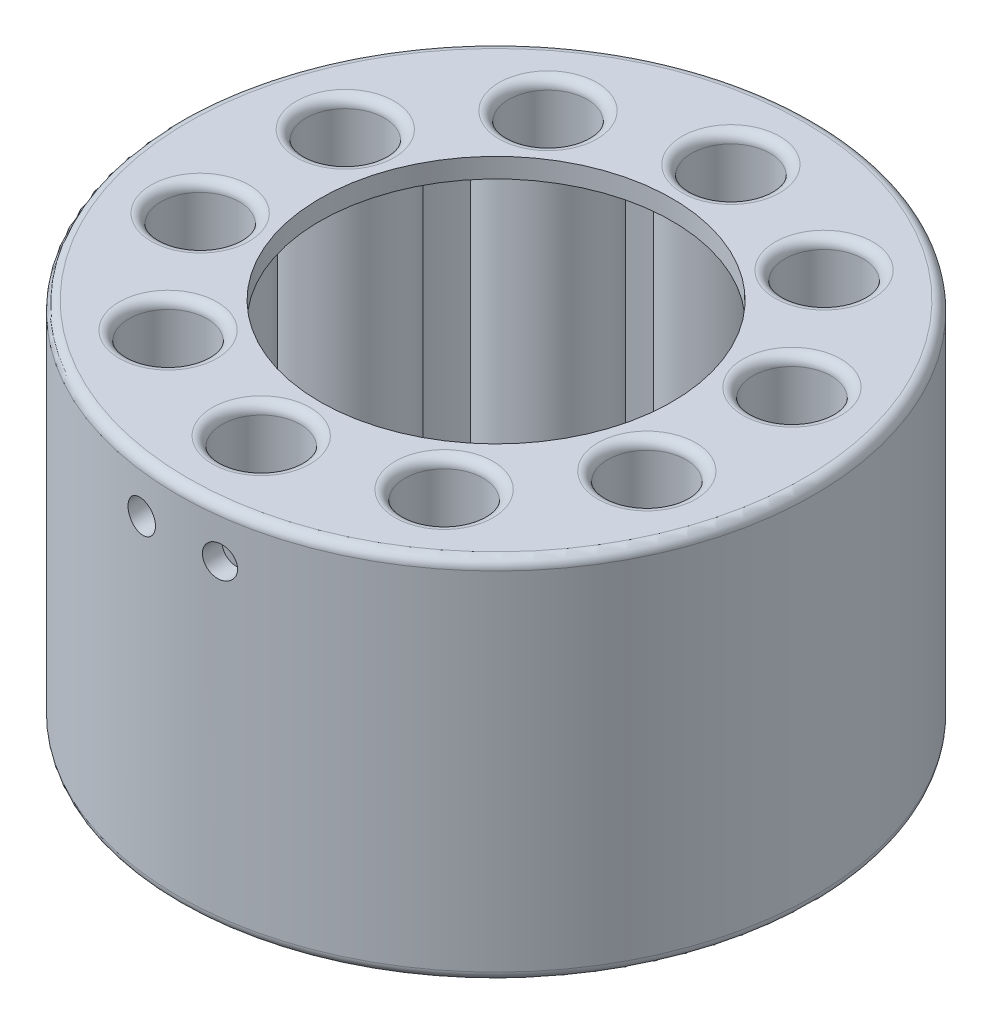
SolidWorks part; units mm, degrees
ref_plane "前视基准面" through (0, 0, 0) normal (0, 0, 1) x (1, 0, 0)
ref_plane "上视基准面" through (0, 0, 0) normal (0, 1, 0) x (1, 0, 0)
ref_plane "右视基准面" through (0, 0, 0) normal (1, 0, 0) x (0, 0, -1)
sketch "草图5" plane through (0, 0, 0) normal (0, 1, 0) x (1, 0, 0)
  circle A13 centre (0, 0) radius 32.5
  circle A14 centre (0, 0) radius 24 construction
  circle A15 centre (0, 24) radius 4
  circle A16 centre (0, 24) radius 5.6
  circle A17 centre (14.1068, 19.4164) radius 5.6
  circle A18 centre (14.1068, 19.4164) radius 4
  circle A19 centre (0, 0) radius 24 construction
  circle A20 centre (22.8254, 7.4164) radius 5.6
  circle A21 centre (22.8254, 7.4164) radius 4
  circle A22 centre (0, 0) radius 24 construction
  circle A23 centre (22.8254, -7.4164) radius 5.6
  circle A24 centre (22.8254, -7.4164) radius 4
  circle A25 centre (0, 0) radius 24 construction
  circle A26 centre (14.1068, -19.4164) radius 5.6
  circle A27 centre (14.1068, -19.4164) radius 4
  circle A28 centre (0, 0) radius 24 construction
  circle A29 centre (0, -24) radius 5.6
  circle A30 centre (0, -24) radius 4
  circle A31 centre (0, 0) radius 24 construction
  circle A32 centre (-14.1068, -19.4164) radius 5.6
  circle A33 centre (-14.1068, -19.4164) radius 4
  circle A34 centre (0, 0) radius 24 construction
  circle A35 centre (-22.8254, -7.4164) radius 5.6
  circle A36 centre (-22.8254, -7.4164) radius 4
  circle A37 centre (0, 0) radius 24 construction
  circle A38 centre (-22.8254, 7.4164) radius 5.6
  circle A39 centre (-22.8254, 7.4164) radius 4
  circle A40 centre (0, 0) radius 24 construction
  circle A41 centre (-14.1068, 19.4164) radius 5.6
  circle A42 centre (-14.1068, 19.4164) radius 4
  circle A43 centre (0, 0) radius 24 construction
  circle A44 centre (0, 0) radius 30.5
  point P45 (0, 0)
  dimension "D1" = 10
extrude "凸台-拉伸1" add sketch "草图5" along normal blind 2.5 contours A15 | A39 | A13 | A36 | A42 | A18 | A21 | A24 | A27 | A30 | A33 region at (0, 0, -24)
extrude "凸台-拉伸2" add sketch "草图5<4>" along normal blind 37.5 contours A13 | A44 | A41 | A42 | A15 | A16 | A17 | A18 | A20 | A21 | A23 | A24 | A27 | A26 | A30 | A29 | A32 | A33 | A36 | A35 | A38 | A39
sketch "草图5<4>" plane through (0, 0, 0) normal (0, 1, 0) x (1, 0, 0) same geometry as "草图5"
sketch "草图6" plane through (0, 37.5, 0) normal (0, 1, 0) x (1, 0, 0)
  circle A0 centre (0, 0) radius 32
extrude "凸台-拉伸3" add sketch "草图6" against normal blind 2
extrude "切除-拉伸1" cut sketch "草图5<5>" along normal blind 80 contours A39 | A36 | A33 | A30 | A27 | A24 | A21 | A18 | A15 | A42 region at (0, 0, -24) region at (14.1068, 0, -19.4164) region at (22.8254, 0, -7.4164) region at (22.8254, 0, 7.4164) region at (14.1068, 0, 19.4164) region at (0, 0, 24) region at (-14.1068, 0, 19.4164) region at (-22.8254, 0, 7.4164) region at (-22.8254, 0, -7.4164) region at (-14.1068, 0, -19.4164)
sketch "草图5<5>" plane through (0, 0, 0) normal (0, 1, 0) x (1, 0, 0) same geometry as "草图5"
fillet "圆角1" radius 1 2 edges at (0, 37.5, 32.5) (0, 0, 32.5)
fillet "圆角2" radius 1 10 edges at (-22.8254, 37.5, -3.4164) (-22.8254, 37.5, 11.4164) (-14.1068, 37.5, 23.4164) (0, 37.5, 28) (14.1068, 37.5, 23.4164) (22.8254, 37.5, 11.4164) (22.8254, 37.5, -3.4164) (14.1068, 37.5, -15.4164) (0, 37.5, -20) (-14.1068, 37.5, -15.4164)
sketch "草图8" plane through (0, 0, 0) normal (0, -1, 0) x (1, 0, 0)
  circle A0 centre (0, 0) radius 7 construction
  circle A1 centre (0, 7) radius 1.6
  circle A2 centre (7, 0) radius 1.6
  circle A3 centre (0, -7) radius 1.6
  circle A4 centre (-7, 0) radius 1.6
  circle A5 centre (0, 0) radius 2.8
  point P14 (0, 0)
extrude "切除-拉伸2" cut sketch "草图8" against normal blind 5
sketch "草图9" plane through (0, 37.5, 0) normal (0, 1, 0) x (1, 0, 0)
  line L0 (5.9771, 4) -> (5.9771, -4) construction
  line L1 (6.706, 4) -> (6.706, -4)
  line L2 (5.2482, 4) -> (5.2482, -4)
  circle A0 centre (0, 0) radius 4 construction
  arc A1 (6.706, 4) -> (5.2482, 4) centre (5.9771, 4) ccw
  arc A2 (5.2482, -4) -> (6.706, -4) centre (5.9771, -4) ccw
  point P5 (5.9771, 0)
sketch "草图10" plane through (0, 37.5, 0) normal (0, 1, 0) x (1, 0, 0)
  line L0 (4, -2) -> (4, 2)
  line L1 (6, 2) -> (4, 2)
  line L2 (6, 2) -> (6, -2)
  line L3 (6, -2) -> (4, -2)
  line L4 (-6, 2) -> (-6, -2)
  line L5 (-4, 0) -> (-4, 2)
  line L6 (6, 0) -> (4, 0) construction
  line L7 (-4, 0) -> (-4, -2)
  line L8 (-4, -2) -> (-6, -2)
  line L9 (-4, 0) -> (-6, 0) construction
  line L10 (-4, 2) -> (-6, 2)
  point P0 (0, 0)
sketch "草图11" plane through (0, 0, 0) normal (0, 0, 1) x (1, 0, 0)
  line L1 (2.1785, 40.4655) -> (-3.8215, 40.4655)
  line L2 (2.1785, 40.4655) -> (2.1785, 43.4655)
  line L3 (2.1785, 43.4655) -> (-3.8215, 43.4655)
  line L4 (-3.8215, 40.4655) -> (-3.8215, 43.4655)
  line L5 (-0.8215, 43.4655) -> (-0.8215, 40.4655) construction
  line L6 (2.1785, 41.9655) -> (-3.8215, 41.9655) construction
  point P0 (-0.8215, 41.9655)
ref_plane "基准面1" through (0, 0, 41.3594) normal (0, 0, 1) x (1, 0, 0)
ref_plane "基准面2" through (0, 0, -39.7781) normal (0, 0, 1) x (1, 0, 0)
sketch "草图15" plane through (0, 0, 41.3594) normal (0, 0, 1) x (1, 0, 0)
  line L0 (0, 37.5) -> (0, 32.5) construction
  line L1 (5, 37.5) -> (-5, 37.5) construction
  circle A0 centre (0, 32.5) radius 4 construction
  circle A1 centre (-4, 32.5) radius 1.6
  circle A2 centre (4, 32.5) radius 1.6
extrude "切除-拉伸3" cut sketch "草图15" against normal blind 12
sketch "草图17" plane through (0, 0, -39.7781) normal (0, 0, 1) x (1, 0, 0)
  line L0 (0, 37.5) -> (0, 32.5) construction
  line L1 (5, 37.5) -> (-5, 37.5) construction
  circle A0 centre (0, 32.5) radius 4 construction
  circle A1 centre (4, 32.5) radius 1.6
  circle A2 centre (-4, 32.5) radius 1.6
extrude "切除-拉伸4" cut sketch "草图17" along normal blind 10
sketch "草图18" plane through (0, 37.5, 0) normal (0, 1, 0) x (1, 0, 0)
  circle A0 centre (0, 0) radius 18
extrude "切除-拉伸5" cut sketch "草图18" against normal blind 12
